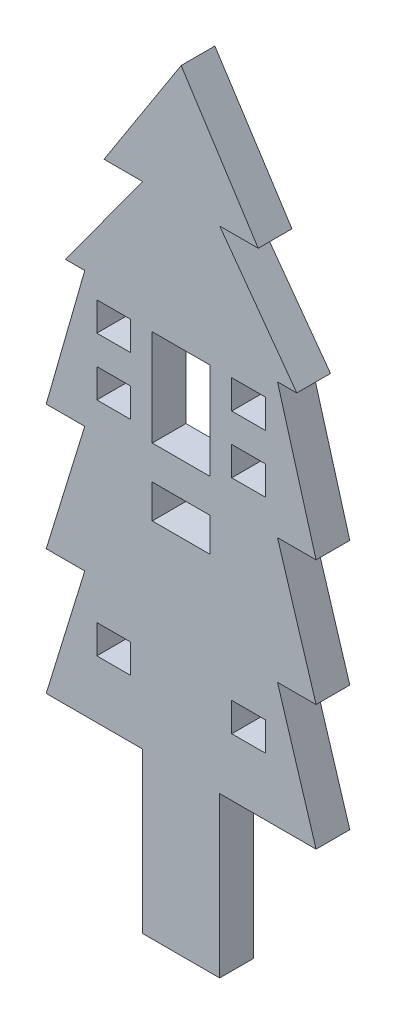
SolidWorks part; units mm, degrees
ref_plane "Ebene vorne (XY)" through (0, 0, 0) normal (0, 0, 1) x (1, 0, 0)
ref_plane "Ebene oben  (XZ)" through (0, 0, 0) normal (0, 1, 0) x (1, 0, 0)
ref_plane "Ebene rechts  (YZ)" through (0, 0, 0) normal (1, 0, 0) x (0, 0, -1)
ref_axis "x-Achse" through (-15.4, 0, 0) along (1, 0, 0)
ref_axis "y-Achse" through (0, 34.4272, 0) along (0, -1, 0)
ref_axis "z-Achse" through (0, 0, -0.175) along (0, 0, 1)
sketch "Profile_Laser_profile_3p5" plane through (0, 0, 0) normal (0, 0, 1) x (1, 0, 0)
  line L0 (0, 30.4272) -> (8, 18)
  line L1 (8, 18) -> (4, 18)
  line L2 (4, 18) -> (12, 7)
  line L3 (12, 7) -> (10, 7)
  line L4 (10, 7) -> (14, -7)
  line L5 (14, -7) -> (10, -7)
  line L6 (10, -7) -> (14, -20)
  line L7 (14, -20) -> (10, -20)
  line L8 (10, -20) -> (14, -33)
  line L9 (14, -33) -> (4, -33)
  line L10 (4, -33) -> (4, -49.5728)
  line L11 (4, -49.5728) -> (-4, -49.5728)
  line L12 (-4, -49.5728) -> (-4, -33)
  line L13 (-4, -33) -> (-14, -33)
  line L14 (-14, -33) -> (-10, -20)
  line L15 (-10, -20) -> (-14, -20)
  line L16 (-14, -20) -> (-10, -7)
  line L17 (-10, -7) -> (-14, -7)
  line L18 (-14, -7) -> (-10, 7)
  line L19 (-10, 7) -> (-12, 7)
  line L20 (-12, 7) -> (-4, 18)
  line L21 (-4, 18) -> (-8, 18)
  line L22 (-8, 18) -> (0, 30.4272)
  line L23 (-8.75, 2) -> (-5.25, 2)
  line L24 (-5.25, 2) -> (-5.25, 5)
  line L25 (-5.25, 5) -> (-8.75, 5)
  line L26 (-8.75, 5) -> (-8.75, 2)
  line L27 (-8.75, -4) -> (-5.25, -4)
  line L28 (-5.25, -4) -> (-5.25, -1)
  line L29 (-5.25, -1) -> (-8.75, -1)
  line L30 (-8.75, -1) -> (-8.75, -4)
  line L31 (-8.75, -27) -> (-5.25, -27)
  line L32 (-5.25, -27) -> (-5.25, -24)
  line L33 (-5.25, -24) -> (-8.75, -24)
  line L34 (-8.75, -24) -> (-8.75, -27)
  line L35 (5.25, 2) -> (8.75, 2)
  line L36 (8.75, 2) -> (8.75, 5)
  line L37 (8.75, 5) -> (5.25, 5)
  line L38 (5.25, 5) -> (5.25, 2)
  line L39 (5.25, -4) -> (8.75, -4)
  line L40 (8.75, -4) -> (8.75, -1)
  line L41 (8.75, -1) -> (5.25, -1)
  line L42 (5.25, -1) -> (5.25, -4)
  line L43 (5.25, -27) -> (8.75, -27)
  line L44 (8.75, -27) -> (8.75, -24)
  line L45 (8.75, -24) -> (5.25, -24)
  line L46 (5.25, -24) -> (5.25, -27)
  line L47 (-3, -12) -> (3, -12)
  line L48 (3, -12) -> (3, -8.5)
  line L49 (3, -8.5) -> (-3, -8.5)
  line L50 (-3, -8.5) -> (-3, -12)
  line L51 (-3, -5) -> (3, -5)
  line L52 (3, -5) -> (3, 5)
  line L53 (3, 5) -> (-3, 5)
  line L54 (-3, 5) -> (-3, -5)
extrude "Laser_profile_3p5" add sketch "Profile_Laser_profile_3p5" along normal blind 3.5
